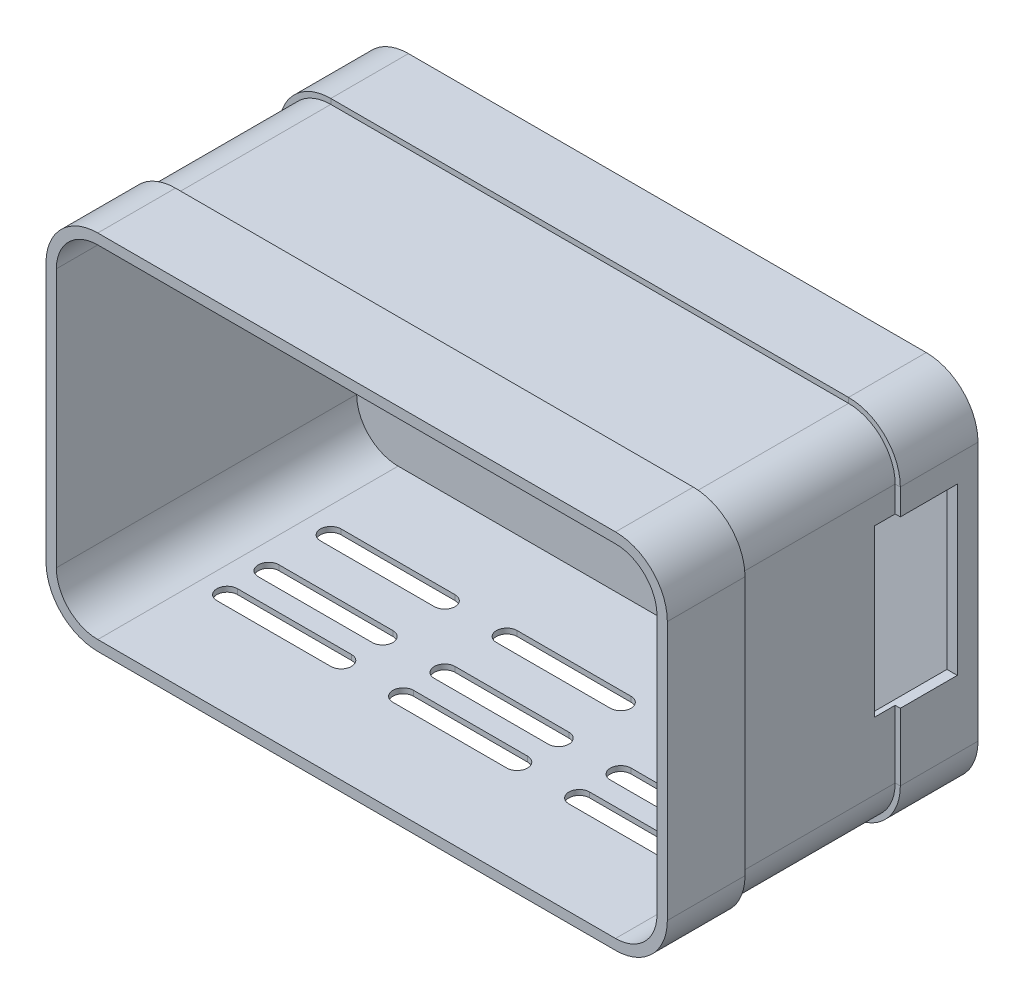
SolidWorks part; units mm, degrees
material "1.0045 (S355JR)"
ref_plane "Plan de face" through (0, 0, 0) normal (0, 0, 1) x (1, 0, 0)
ref_plane "Plan de dessus" through (0, 0, 0) normal (0, 1, 0) x (1, 0, 0)
ref_plane "Plan de droite" through (0, 0, 0) normal (1, 0, 0) x (0, 0, -1)
sketch "Esquisse5" plane through (0, 0, 0) normal (0, 0, 1) x (1, 0, 0)
  line L1 (-50, -35) -> (50, -35)
  line L2 (-60, -25) -> (-60, 25)
  line L3 (-50, 35) -> (50, 35)
  line L4 (60, -25) -> (60, 25)
  line L5 (0, 35) -> (0, -35) construction
  line L6 (-60, 0) -> (60, 0) construction
  arc A0 (-50, -35) -> (-60, -25) centre (-50, -25) cw
  arc A1 (50, -35) -> (60, -25) centre (50, -25) ccw
  arc A2 (50, 35) -> (60, 25) centre (50, 25) cw
  arc A3 (-60, 25) -> (-50, 35) centre (-50, 25) cw
  point P0 (0, 0)
  point P11 (60, -35)
  point P14 (60, 35)
  point P17 (-60, 35)
  dimension "D3" = 10
  dimension "D1" = 120
  dimension "D2" = 70
extrude "Boss.-Extru.2" add sketch "Esquisse5" along normal mid plane 60
shell "Coque2" thickness 2 removed face at (0, 0, 30)
sketch "Esquisse11" plane through (0, 0, 0) normal (0, 1, 0) x (1, 0, 0)
  line L0 (-60, -30) -> (-60, 30) construction
  line L1 (-61, -15) -> (-59, -15)
  line L2 (-61, -15) -> (-61, 15)
  line L3 (-61, 15) -> (-59, 15)
  line L4 (-59, -15) -> (-59, 15)
  line L5 (-60, 15) -> (-60, -15) construction
  line L6 (-61, 0) -> (-59, 0) construction
  point P0 (-60, 0)
  dimension "D1" = 2
  dimension "D2" = 30
sweep "Enlèvement de matière-Balayage11" cut profiles "Esquisse11" path "Esquisse5<5>"
sketch "Esquisse5<5>" plane through (0, 0, 0) normal (0, 0, 1) x (1, 0, 0) same geometry as "Esquisse5"
sketch "Esquisse16" plane through (0, -34, 0) normal (0, -1, 0) x (1, 0, 0)
  line L0 (22.9969, 10) -> (44.9969, 10) construction
  line L1 (22.9969, 12) -> (44.9969, 12)
  line L2 (22.9969, 8) -> (44.9969, 8)
  line L3 (-11.0031, 10) -> (10.9969, 10) construction
  line L4 (-11.0031, 12) -> (10.9969, 12)
  line L5 (-11.0031, 8) -> (10.9969, 8)
  line L6 (-45, 10) -> (-23, 10) construction
  line L7 (-45, 12) -> (-23, 12)
  line L8 (-45, 8) -> (-23, 8)
  line L9 (-50.3717, 6) -> (49.6283, 6) construction
  line L10 (22.9969, 2) -> (44.9969, 2) construction
  line L11 (22.9969, 0) -> (44.9969, 0)
  line L12 (22.9969, 4) -> (44.9969, 4)
  line L13 (-11.0031, 2) -> (10.9969, 2) construction
  line L14 (-11.0031, 0) -> (10.9969, 0)
  line L15 (-11.0031, 4) -> (10.9969, 4)
  line L16 (-45, 2) -> (-23, 2) construction
  line L17 (-45, 0) -> (-23, 0)
  line L18 (-45, 4) -> (-23, 4)
  line L19 (-50.3717, -4) -> (49.6283, -4) construction
  line L20 (-45, -10) -> (-23, -10) construction
  line L21 (-45, -8) -> (-23, -8)
  line L22 (-45, -12) -> (-23, -12)
  line L23 (-11.0031, -10) -> (10.9969, -10) construction
  line L24 (-11.0031, -8) -> (10.9969, -8)
  line L25 (-11.0031, -12) -> (10.9969, -12)
  line L26 (22.9969, -10) -> (44.9969, -10) construction
  line L27 (22.9969, -8) -> (44.9969, -8)
  line L28 (22.9969, -12) -> (44.9969, -12)
  line L29 (-50, 15) -> (-50, -15) construction
  line L30 (50, 15) -> (-50, 15) construction
  arc A0 (22.9969, 12) -> (22.9969, 8) centre (22.9969, 10) ccw
  arc A1 (44.9969, 8) -> (44.9969, 12) centre (44.9969, 10) ccw
  arc A2 (-11.0031, 12) -> (-11.0031, 8) centre (-11.0031, 10) ccw
  arc A3 (10.9969, 8) -> (10.9969, 12) centre (10.9969, 10) ccw
  arc A4 (-45, 12) -> (-45, 8) centre (-45, 10) ccw
  arc A5 (-23, 8) -> (-23, 12) centre (-23, 10) ccw
  arc A6 (22.9969, 0) -> (22.9969, 4) centre (22.9969, 2) cw
  arc A7 (44.9969, 4) -> (44.9969, 0) centre (44.9969, 2) cw
  arc A8 (-11.0031, 0) -> (-11.0031, 4) centre (-11.0031, 2) cw
  arc A9 (10.9969, 4) -> (10.9969, 0) centre (10.9969, 2) cw
  arc A10 (-45, 0) -> (-45, 4) centre (-45, 2) cw
  arc A11 (-23, 4) -> (-23, 0) centre (-23, 2) cw
  arc A12 (-45, -8) -> (-45, -12) centre (-45, -10) ccw
  arc A13 (-23, -12) -> (-23, -8) centre (-23, -10) ccw
  arc A14 (-11.0031, -8) -> (-11.0031, -12) centre (-11.0031, -10) ccw
  arc A15 (10.9969, -12) -> (10.9969, -8) centre (10.9969, -10) ccw
  arc A16 (22.9969, -8) -> (22.9969, -12) centre (22.9969, -10) ccw
  arc A17 (44.9969, -12) -> (44.9969, -8) centre (44.9969, -10) ccw
  point P2 (33.9969, 10)
  point P7 (-0.0031, 10)
  point P14 (-34, 10)
  point P25 (33.9969, 2)
  point P32 (-0.0031, 2)
  point P39 (-34, 2)
  point P48 (-34, -10)
  point P55 (-0.0031, -10)
  point P62 (33.9969, -10)
  dimension "D6" = 5
  dimension "D1" = 4
  dimension "D2" = 4
  dimension "D3" = 4
  dimension "D4" = 4
  dimension "D5" = 4
  dimension "D7" = 11.9969
  dimension "D8" = 12
  dimension "D9" = 22
  dimension "D10" = 22
  dimension "D11" = 22
  dimension "D12" = 3
extrude "Enlèv. mat.-Extru.2" cut sketch "Esquisse16" against normal mid plane 10
sketch "Esquisse17" plane through (60, 0, 0) normal (1, 0, 0) x (0, 0, -1)
  line L1 (11, -12) -> (26, -12)
  line L2 (11, -12) -> (11, 20)
  line L3 (11, 20) -> (26, 20)
  line L4 (26, -12) -> (26, 20)
  line L5 (18.5, 20) -> (18.5, -12) construction
  line L6 (11, 4) -> (26, 4) construction
  line L7 (15, 25) -> (30, 25) construction
  line L8 (30, -25) -> (30, 25) construction
  line L9 (15, -25) -> (30, -25) construction
  dimension "D1" = 5
  dimension "D2" = 32
  dimension "D3" = 4
  dimension "D4" = 13
  dimension "D5" = 15
extrude "Enlèv. mat.-Extru.3" cut sketch "Esquisse17" against normal blind 10
